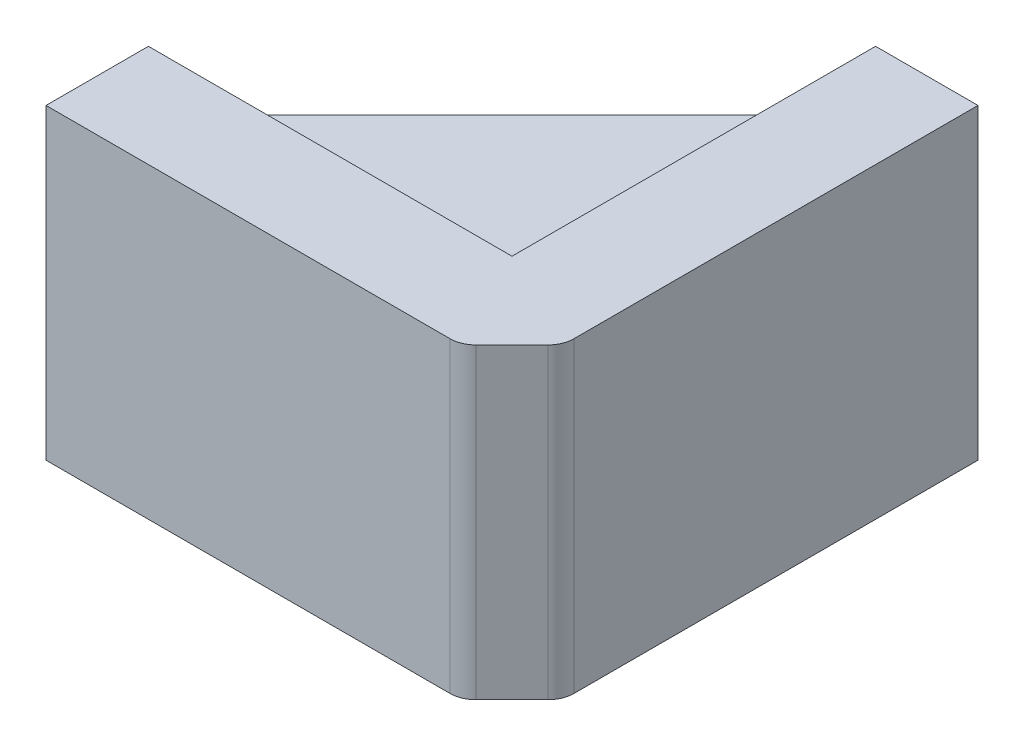
SolidWorks part; units mm, degrees
material "ABS"
ref_plane "Alzado" through (0, 0, 0) normal (0, 0, 1) x (1, 0, 0)
ref_plane "Planta" through (0, 0, 0) normal (0, 1, 0) x (1, 0, 0)
ref_plane "Vista lateral" through (0, 0, 0) normal (1, 0, 0) x (0, 0, -1)
sketch "Sketch1" plane through (0, 0, 0) normal (0, 1, 0) x (1, 0, 0)
  line L0 (25.5, 45.5) -> (25.5, -25.5)
  line L1 (-45.5, -45.5) -> (45.5, -45.5)
  line L2 (-45.5, -45.5) -> (-45.5, 45.5) construction
  line L3 (-45.5, 45.5) -> (45.5, 45.5) construction
  line L4 (45.5, -45.5) -> (45.5, 45.5)
  line L5 (-45.5, -45.5) -> (45.5, 45.5) construction
  line L6 (-45.5, 45.5) -> (45.5, -45.5) construction
  line L7 (25.5, -25.5) -> (-45.5, -25.5)
  line L8 (-45.5, -25.5) -> (-45.5, -45.5)
  line L9 (25.5, 45.5) -> (45.5, 45.5)
  point P0 (0, 0)
  dimension "D1" = 71
  dimension "D3" = 20
extrude "Boss-Extrude1" add sketch "Sketch1" along normal blind 60
chamfer "Chamfer1" distance 10 angle 45 1 edges at (45.5, 30, 45.5)
fillet "Fillet1" radius 5 2 edges at (45.5, 30, 35.5) (35.5, 30, 45.5)
sketch "Sketch2" plane through (0, 60, 0) normal (0, 1, 0) x (1, 0, 0)
  line L0 (25.5, 31.0685) -> (-31.0685, -25.5)
  line L1 (25.5, 45.5) -> (25.5, -25.5) construction
  line L2 (25.5, -25.5) -> (-45.5, -25.5) construction
  line L3 (-31.0685, -25.5) -> (25.5, -25.5)
  line L4 (25.5, -25.5) -> (25.5, 31.0685)
  line L5 (36.9645, -44.0355) -> (44.0355, -36.9645) construction
  point P6 (25.5, 38.8526)
  dimension "D1" = 40
extrude "Boss-Extrude2" add sketch "Sketch2" against normal blind 5 from offset 4.4 offset against normal yes
